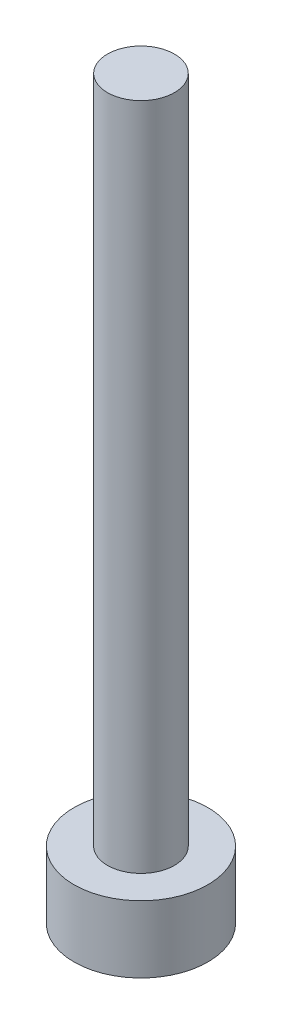
SolidWorks part; units mm, degrees
ref_plane "Front Plane" through (0, 0, 0) normal (0, 0, 1) x (1, 0, 0)
ref_plane "Top Plane" through (0, 0, 0) normal (0, 1, 0) x (1, 0, 0)
ref_plane "Right Plane" through (0, 0, 0) normal (1, 0, 0) x (0, 0, -1)
sketch "Sketch1" plane through (0, 0, 0) normal (0, 1, 0) x (1, 0, 0)
  circle A0 centre (0, 0) radius 3
  dimension "D1" = 6
extrude "Boss-Extrude1" add sketch "Sketch1" along normal blind 3
sketch "Sketch2" plane through (0, 3, 0) normal (0, 1, 0) x (1, 0, 0)
  circle A0 centre (0, 0) radius 1.5
  dimension "D1" = 3
extrude "Boss-Extrude2" add sketch "Sketch2" along normal blind 30 contours A0
